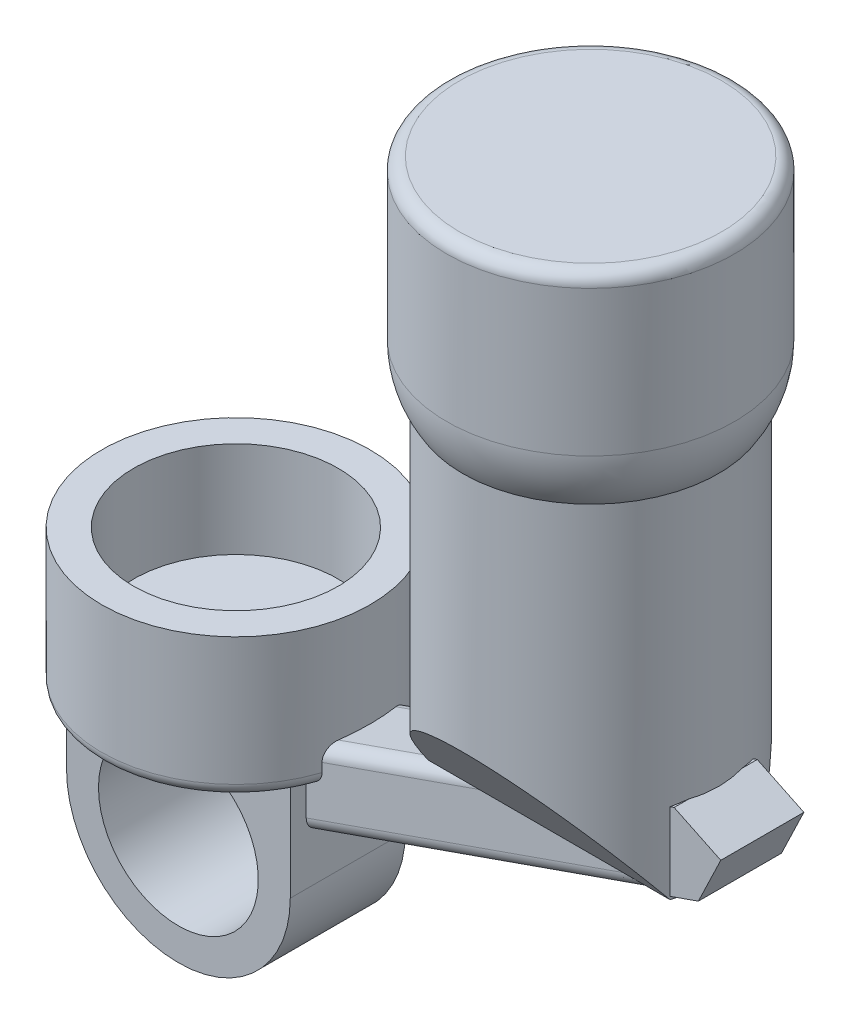
SolidWorks part; units mm, degrees
ref_plane "Front Plane" through (0, 0, 0) normal (0, 0, 1) x (1, 0, 0)
ref_plane "Top Plane" through (0, 0, 0) normal (0, 1, 0) x (1, 0, 0)
ref_plane "Right Plane" through (0, 0, 0) normal (1, 0, 0) x (0, 0, -1)
sketch "Sketch1" plane through (0, 0, 0) normal (0, 1, 0) x (1, 0, 0)
  circle A0 centre (0, 0) radius 21
  dimension "D1" = 42
extrude "Boss-Extrude1" add sketch "Sketch1" along normal blind 22
sketch "Sketch3" plane through (0, 0, 0) normal (0, -1, 0) x (1, 0, 0)
  line L1 (17.5, 9) -> (-17.5, 9)
  line L2 (17.5, 9) -> (17.5, -9)
  line L3 (17.5, -9) -> (-17.5, -9)
  line L4 (-17.5, 9) -> (-17.5, -9)
  line L5 (17.5, 9) -> (-17.5, -9) construction
  line L6 (17.5, -9) -> (-17.5, 9) construction
  point P0 (0, 0)
  dimension "D1" = 35
  dimension "D2" = 18
extrude "Boss-Extrude2" add sketch "Sketch3" along normal blind 15
sketch "Sketch4" plane through (0, 0, 9) normal (0, 0, 1) x (1, 0, 0)
  line L1 (17.5, -15) -> (-17.5, -15) construction
  line L2 (-17.5, -15) -> (17.5, -15)
  line L3 (17.5, -15) -> (-17.5, -15)
  arc A1 (-17.5, -15) -> (17.5, -15) centre (0, -15) ccw
  dimension "D1" = 35
sketch "Sketch5" plane through (0, 0, 0) normal (0, 0, 1) x (1, 0, 0)
  line L0 (-17.5, -15) -> (17.5, -15) construction
  line L1 (-17.5, -15) -> (17.5, -15)
  arc A0 (-17.5, -15) -> (17.5, -15) centre (0, -15) ccw construction
  arc A1 (-17.5, -15) -> (17.5, -15) centre (0, -15) ccw
extrude "Boss-Extrude3" add sketch "Sketch5" along normal mid plane 18
sketch "Sketch6" plane through (0, 0, -9) normal (0, 0, -1) x (-1, 0, 0)
  circle A0 centre (0, -15) radius 12.5
  arc A1 (-17.5, -15) -> (17.5, -15) centre (0, -15) ccw construction
  dimension "D1" = 25
extrude "Cut-Extrude1" cut sketch "Sketch6" against normal blind 18
sketch "Sketch7" plane through (0, 0, 0) normal (0, 0, 1) x (1, 0, 0)
  line L0 (17.5, -7.5) -> (88.2733, 17.3221)
  line L1 (17.5, -15) -> (17.5, 0) construction
  line L2 (88.2733, 17.3221) -> (84.4848, 28.124)
  line L3 (84.4848, 28.124) -> (17.5, 4.6307)
  line L4 (17.5, 4.6307) -> (17.5, -7.5)
  dimension "D1" = 75
extrude "Boss-Extrude5" add sketch "Sketch7" along normal mid plane 13
ref_plane "Plane2" through (0, 12, 0) normal (0, 1, 0) x (1, 0, 0)
sketch "Sketch9" plane through (0, 12, 0) normal (0, 1, 0) x (1, 0, 0)
  line L1 (84.4848, -6.5) -> (84.4848, 6.5) construction
  circle A0 centre (55.4848, 0) radius 20
  dimension "D1" = 40
  dimension "D2" = 29
extrude "Boss-Extrude6" add sketch "Sketch9" along normal blind 55
sketch "Sketch10" plane through (0, 67, 0) normal (0, 1, 0) x (1, 0, 0)
  circle A0 centre (55.4848, 0) radius 22.5
  circle A1 centre (55.4848, 0) radius 20 construction
  dimension "D1" = 45
extrude "Boss-Extrude7" add sketch "Sketch10" along normal blind 33
fillet "Fillet1" radius 15 1 edges at (55.4848, 67, 22.5)
chamfer "Chamfer2" distance 10 angle 45 2 edges at (84.4848, 28.124, 0) (88.2733, 17.3221, 0)
fillet "Fillet3" radius 2 4 edges at (45.2994, 2.25, -6.5) (29.2402, 8.7483, -6.5) (29.2402, 8.7483, 6.5) (45.2994, 2.25, 6.5)
fillet "Fillet4" radius 2 1 edges at (-21, 0, 0)
fillet "Fillet5" radius 2 1 edges at (55.4848, 100, 22.5)
ref_plane "Plane3" through (55, 0, 0) normal (1, 0, 0) x (0, 0, -1)
sketch "Sketch12" plane through (55, 0, 0) normal (1, 0, 0) x (0, 0, -1)
  line L0 (6.5, 12) -> (20, 29.2837)
  line L1 (20, 12) -> (20, 67) construction
  line L2 (20, 29.2837) -> (20, 12)
  line L3 (20, 12) -> (6.5, 12)
  line L4 (4.5, 12) -> (6.5, 12) construction
  line L5 (0, 56.839) -> (0, -56.839) construction
  line L6 (-20, 12) -> (-6.5, 12)
  line L7 (-20, 29.2837) -> (-20, 12)
  line L8 (-6.5, 12) -> (-20, 29.2837)
extrude "Cut-Extrude4" cut sketch "Sketch12" against normal mid plane 50
sketch "Sketch13" plane through (0, 22, 0) normal (0, 1, 0) x (1, 0, 0)
  circle A0 centre (0, 0) radius 16
  circle A1 centre (0, 0) radius 21 construction
  dimension "D1" = 5
extrude "Cut-Extrude6" cut sketch "Sketch13" against normal blind 15
